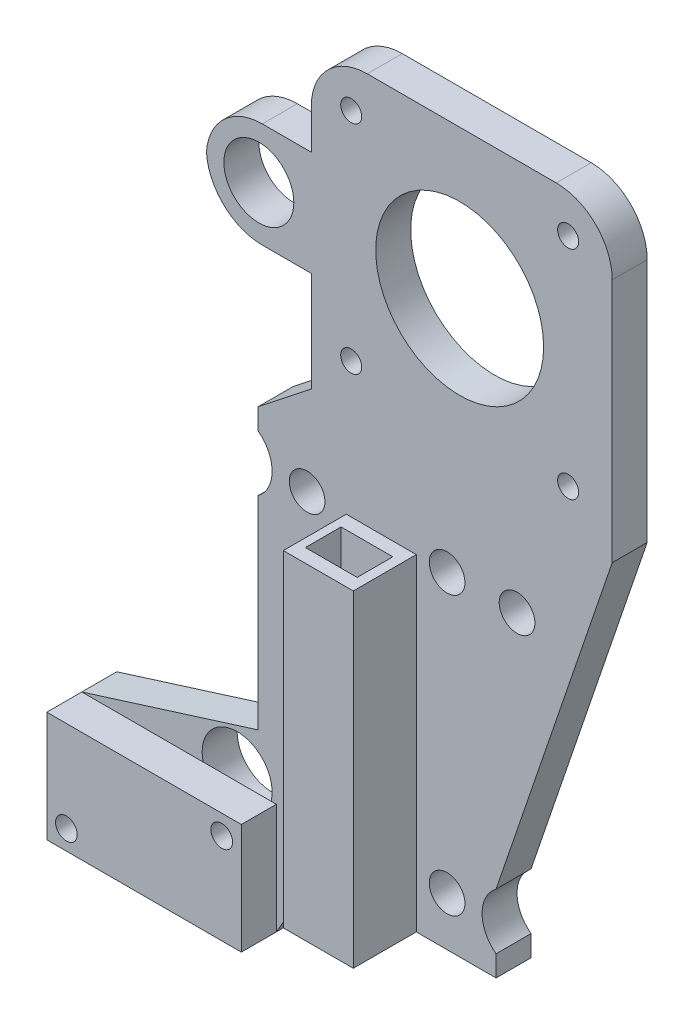
SolidWorks part; units mm, degrees
ref_plane "Front Plane" through (0, 0, 0) normal (0, 0, 1) x (1, 0, 0)
ref_plane "Top Plane" through (0, 0, 0) normal (0, 1, 0) x (1, 0, 0)
ref_plane "Right Plane" through (0, 0, 0) normal (1, 0, 0) x (0, 0, -1)
sketch "Sketch1" plane through (0, 0, 0) normal (0, 0, 1) x (1, 0, 0)
  line L0 (7, 46.7) -> (27, 46.7) construction
  line L1 (0, 0) -> (34, 0)
  line L2 (0, 0) -> (0, 3)
  line L3 (0, 53.7) -> (34, 53.7)
  line L4 (34, 0) -> (34, 3)
  line L5 (27, 46.7) -> (27, 7) construction
  line L6 (27, 7) -> (7, 7) construction
  line L7 (7, 7) -> (7, 46.7) construction
  line L8 (-3, 46.7) -> (37, 46.7) construction
  line L9 (37, 46.7) -> (37, 7) construction
  line L10 (37, 7) -> (-3, 7) construction
  line L11 (-3, 7) -> (-3, 46.7) construction
  line L12 (0, 50.7) -> (0, 53.7)
  line L13 (34, 50.7) -> (34, 53.7)
  line L14 (34, 11) -> (34, 42.7)
  line L15 (0, 11) -> (0, 42.7)
  circle A0 centre (7, 46.7) radius 2.55
  circle A1 centre (27, 46.7) radius 2.55
  circle A2 centre (7, 7) radius 2.55
  circle A3 centre (27, 7) radius 2.55
  arc A4 (0, 42.7) -> (0, 50.7) centre (-3, 46.7) ccw
  arc A5 (34, 50.7) -> (34, 42.7) centre (37, 46.7) ccw
  arc A6 (34, 11) -> (34, 3) centre (37, 7) ccw
  arc A7 (0, 3) -> (0, 11) centre (-3, 7) ccw
  dimension "D3" = 5.1
  dimension "D10" = 10
  dimension "D1" = 20
  dimension "D2" = 39.7
  dimension "D4" = 7
  dimension "D5" = 7
  dimension "D6" = 7
  dimension "D7" = 7
  dimension "D8" = 10
  dimension "D9" = 10
extrude "Boss-Extrude1" add sketch "Sketch1" along normal blind 5
sketch "Sketch2" plane through (0, 0, 5) normal (0, 0, 1) x (1, 0, 0)
  line L0 (7, 46.7) -> (27, 46.7) construction
  line L1 (12.6, 46.7) -> (22.6, 46.7)
  line L2 (12.6, 46.7) -> (12.6, 0)
  line L3 (12.6, 0) -> (22.6, 0)
  line L4 (22.6, 46.7) -> (22.6, 0)
  line L5 (7, 7) -> (27, 7) construction
  line L8 (0, 0) -> (34, 0) construction
  line L9 (0, 42.7) -> (0, 11) construction
  circle A0 centre (7, 7) radius 2.55 construction
  circle A1 centre (27, 7) radius 2.55 construction
  circle A2 centre (27, 46.7) radius 2.55 construction
  circle A3 centre (7, 46.7) radius 2.55 construction
  circle A4 centre (7, 7) radius 2.55
  circle A5 centre (27, 7) radius 2.55
  circle A6 centre (27, 46.7) radius 2.55
  circle A7 centre (7, 46.7) radius 2.55
  dimension "D1" = 10
  dimension "D2" = 12.6
extrude "Boss-Extrude2" add sketch "Sketch2" along normal blind 9 contours L4 L1 L2 L3 region at (17.6, 23.35, 5)
sketch "Sketch3" plane through (0, 0, 5) normal (0, 0, 1) x (1, 0, 0)
  line L0 (12.6, 46.7) -> (12.6, 0) construction
  line L2 (2.6, 5.8) -> (2.6, -10)
  line L3 (2.6, -10) -> (-25.2, -10)
  line L4 (-25.2, 5.8) -> (-25.2, -10)
  line L5 (-25.2, 5.8) -> (2.6, 5.8)
  line L6 (0, 0) -> (12.6, 0) construction
  circle A0 centre (7, 7) radius 4
  line M12 (0, 3) -> (0, 0)
  line M13 (0, 0) -> (12.6, 0)
  arc M23 (0, 11) -> (0, 3) centre (-3, 7) cw
  dimension "D3" = 8
  dimension "D5" = 10
  dimension "D1" = 27.8
  dimension "D2" = 15.8
  dimension "D4" = 10
extrude "Boss-Extrude3" add sketch "Sketch3" along normal blind 5 contours L5 L4 L3 L2 M13 M12 M23 | L5 L2 L3 L4 region at (-11.6533, -2.2243, 5)
sketch "Sketch5" plane through (0, 46.7, 0) normal (0, 1, 0) x (1, 0, 0)
  line L0 (12.6, -9.5) -> (22.6, -9.5) construction
  line L10 (13.8, -6.95) -> (21.2, -6.95)
  line L11 (13.8, -6.95) -> (13.8, -12.05)
  line L12 (13.8, -12.05) -> (21.2, -12.05)
  line L13 (21.2, -6.95) -> (21.2, -12.05)
  line L14 (12.6, -14) -> (12.6, -5) construction
  line L15 (22.6, -14) -> (22.6, -5) construction
  dimension "D1" = 7.4
  dimension "D2" = 5.1
  dimension "D3" = 1.2
extrude "Cut-Extrude2" cut sketch "Sketch5" against normal through all and the other way through all
sketch "Sketch6" plane through (0, 0, 5) normal (0, 0, 1) x (1, 0, 0)
  line L0 (0, 53.7) -> (0, 50.7) construction
  line L5 (7.6, 102.7) -> (50.6, 102.7)
  line L6 (7.6, 102.7) -> (7.6, 59.7)
  line L7 (7.6, 59.7) -> (50.6, 59.7)
  line L8 (50.6, 102.7) -> (50.6, 59.7)
  line L9 (7.6, 59.7) -> (0, 53.7)
  line L10 (0, 53.7) -> (34, 53.7)
  line L11 (34, 53.7) -> (50.6, 59.7)
  circle A0 centre (27, 46.7) radius 2.55 construction
  line M23 (34, 53.7) -> (0, 53.7)
  dimension "D3" = 13
  dimension "D1" = 43
  dimension "D2" = 43
  dimension "D4" = 7.6
extrude "Boss-Extrude4" add sketch "Sketch6" against normal through all contours L8 L5 L6 L7 | L11 L7 L9 M23 region at (29.1, 81.2, 5) region at (23.2857, 56.8169, 5)
sketch "Sketch8" plane through (0, 0, 5) normal (0, 0, 1) x (1, 0, 0)
  line L0 (13.3, 97) -> (44.3, 97) construction
  line L1 (44.3, 97) -> (44.3, 66) construction
  line L2 (44.3, 66) -> (13.3, 66) construction
  line L3 (13.3, 66) -> (13.3, 97) construction
  line L4 (7.6, 102.7) -> (7.6, 59.7) construction
  line L5 (7.6, 102.7) -> (50.6, 102.7) construction
  line L6 (28.8, 97) -> (28.8, 66) construction
  line L7 (13.3, 81.5) -> (44.3, 81.5) construction
  circle A0 centre (13.3, 97) radius 1.5
  circle A1 centre (44.3, 97) radius 1.5
  circle A2 centre (13.3, 66) radius 1.5
  circle A3 centre (44.3, 66) radius 1.5
  circle A4 centre (28.8, 81.5) radius 12
  point P18 (28.8, 81.5)
  dimension "D5" = 3
  dimension "D6" = 24
  dimension "D1" = 5.7
  dimension "D2" = 5.7
  dimension "D3" = 31
  dimension "D4" = 31
extrude "Cut-Extrude3" cut sketch "Sketch8" against normal through all
sketch "Sketch9" plane through (0, 0, 5) normal (0, 0, 1) x (1, 0, 0)
  line L0 (50.6, 59.7) -> (34, 11)
  circle A0 centre (37, 46.7) radius 5
  line M18 (34, 11) -> (34, 42.7)
  line M20 (34, 50.7) -> (34, 53.7)
  line M21 (34, 53.7) -> (50.6, 59.7)
  dimension "D1" = 10
extrude "Boss-Extrude5" add sketch "Sketch9" against normal up to surface (5 mm away) contours A0 L0 M18 M21 M20 region at (39.9791, 40.2387, 5) up to face at (45.8, 97, 0)
sketch "Sketch10" plane through (0, 0, 5) normal (0, 0, 1) x (1, 0, 0)
  circle A0 centre (37, 46.7) radius 2.55
  circle A1 centre (37, 46.7) radius 5 construction
  circle A2 centre (37, 46.7) radius 5
  dimension "D1" = 5.1
extrude "Boss-Extrude6" add sketch "Sketch10" against normal up to surface (5 mm away) up to face at (42, 46.7, 0)
fillet "Fillet1" radius 8 2 edges at (7.6, 102.7, 2.5) (50.6, 102.7, 2.5)
sketch "Sketch11" plane through (0, 0, 5) normal (0, 0, -1) x (-1, 0, 0)
  line L0 (-2.6, -10) -> (-8.3735, 0)
  line L1 (0, 0) -> (-34, 0) construction
  line L2 (-8.3735, 0) -> (0, 0)
  line L3 (0, 0) -> (0, 3)
  line L4 (-2.6, -10) -> (25.2, -10)
  line L5 (25.2, -10) -> (25.2, 5.8)
  line L8 (-2.6, 0) -> (-2.6, -10) construction
  line L9 (25.2, 5.8) -> (0, 13.7054)
  line L10 (0, 42.7) -> (0, 11) construction
  line L11 (0, 13.7054) -> (0, 11)
  arc A1 (0, 3) -> (0, 11) centre (3, 7) ccw
  arc A2 (0, 11) -> (0, 3) centre (3, 7) ccw construction
  dimension "D2" = 5.5
  dimension "D1" = 30
extrude "Boss-Extrude7" add sketch "Sketch11" along normal up to surface (5 mm away) up to face at (45.8, 97, 0)
sketch "Sketch12" plane through (0, 0, 10) normal (0, 0, 1) x (1, 0, 0)
  line L0 (2.6, -10) -> (-25.2, -10) construction
  line L1 (-25.2, 5.8) -> (-25.2, -10) construction
  line L2 (-25.2, 5.8) -> (2.6, 5.8) construction
  line L3 (2.6, 5.8) -> (2.6, -10) construction
  circle A0 centre (-22.4, -7.2) radius 1.55
  circle A1 centre (-0.2, 3) radius 1.55
  dimension "D1" = 3.1
  dimension "D2" = 2.8
  dimension "D3" = 2.8
  dimension "D4" = 2.8
  dimension "D5" = 2.8
extrude "Cut-Extrude4" cut sketch "Sketch12" against normal up to surface (10 mm away) up to face at (13.9514, 39.8894, 0)
sketch "Sketch13" plane through (0, 0, 5) normal (0, 0, 1) x (1, 0, 0)
  line L0 (7.6, 94.7) -> (7.6, 59.7) construction
  line L1 (7.6, 74) -> (-7.4, 74)
  line L2 (7.6, 74) -> (7.6, 89)
  line L3 (7.6, 89) -> (-7.4, 89)
  line L4 (-7.4, 74) -> (-7.4, 89)
  line L5 (0.1, 89) -> (0.1, 74) construction
  line L6 (-7.4, 81.5) -> (7.6, 81.5) construction
  circle A0 centre (0.1, 81.5) radius 5
  circle A1 centre (28.8, 81.5) radius 12 construction
  circle A2 centre (28.8, 81.5) radius 12
  point P12 (0.1, 81.5)
  line M14 (7.6, 94.7) -> (7.6, 59.7)
  dimension "D3" = 10
  dimension "D1" = 15
  dimension "D2" = 15
extrude "Boss-Extrude8" add sketch "Sketch13" along direction (0, 0, 1) on the side against the normal up to surface (5 mm away) contours L4 L1 L3 A0 M14 region at (0.1, 74.2121, 5) up to face at (-20.85, -7.2, 0)
fillet "Fillet2" radius 8 2 edges at (-7.4, 74, 2.5) (-7.4, 89, 2.5)
